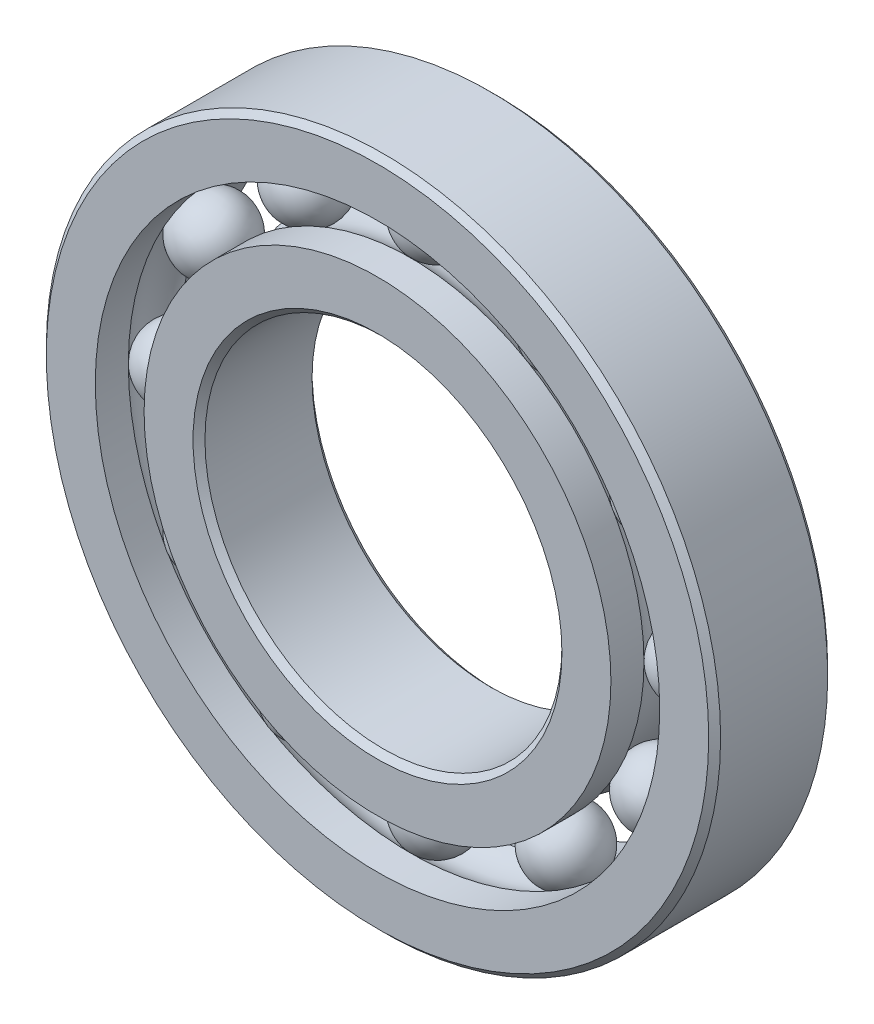
SolidWorks part; units mm, degrees
ref_plane "Front Plane" through (0, 0, 0) normal (0, 0, 1) x (1, 0, 0)
ref_plane "Top Plane" through (0, 0, 0) normal (0, 1, 0) x (1, 0, 0)
ref_plane "Right Plane" through (0, 0, 0) normal (1, 0, 0) x (0, 0, -1)
sketch "Sketch1" plane through (0, 0, 0) normal (1, 0, 0) x (0, 0, -1)
  line L0 (-4.7625, 0) -> (4.7625, 0) construction
  line L1 (0, 26.9875) -> (0, -26.9875) construction
  line L2 (4.2863, 26.9875) -> (-4.2863, 26.9875)
  line L3 (-4.2863, 26.9875) -> (-4.7625, 26.5112)
  line L4 (-4.7625, 26.5112) -> (-4.7625, 22.5913)
  line L5 (-4.7625, 22.5913) -> (-2.1167, 22.5913)
  line L6 (4.7625, 22.5913) -> (2.1167, 22.5913)
  line L7 (4.7625, 26.5112) -> (4.7625, 22.5913)
  line L8 (4.2863, 26.9875) -> (4.7625, 26.5112)
  line L9 (0, 26.9875) -> (0, 20.6375) construction
  line L10 (0, 20.6375) -> (0, 14.2875) construction
  arc A0 (-2.1167, 22.5913) -> (2.1167, 22.5913) centre (0, 20.6375) cw
  point P14 (0, 14.2875)
  dimension "Width" = 9.525
  dimension "OD" = 53.975
  dimension "D1" = 45
  dimension "D2" = 0.4763
  dimension "Shaft Dia" = 28.575
  dimension "D3" = 4.2333
  dimension "D4" = 1.9538
revolve "Revolve1" add sketch "Sketch1" angle 360 about L0
sketch "Sketch3" plane through (0, 0, 0) normal (1, 0, 0) x (0, 0, -1)
  line L0 (-4.7625, 18.6837) -> (-2.1167, 18.6837)
  line L1 (0, 26.9875) -> (0, -26.9875) construction
  line L2 (-4.7625, 26.5112) -> (-4.7625, 22.5913) construction
  line L3 (-4.7625, 18.6837) -> (-4.7625, 14.7638)
  line L4 (-4.2863, 26.9875) -> (-4.7625, 26.5112) construction
  line L5 (-4.7625, 14.7638) -> (-4.2863, 14.2875)
  line L6 (-4.2863, 14.2875) -> (4.2863, 14.2875)
  line L7 (4.2863, 26.9875) -> (4.2863, -26.9875) construction
  line L8 (4.2863, 14.2875) -> (4.7625, 14.7637)
  line L9 (4.7625, -26.5112) -> (4.7625, 26.5112) construction
  line L10 (4.7625, 14.7637) -> (4.7625, 18.6837)
  line L11 (4.7625, 18.6837) -> (2.1167, 18.6837)
  line L13 (4.2863, 26.9875) -> (4.7625, 26.5112) construction
  arc A0 (2.1167, 22.5913) -> (-2.1167, 22.5913) centre (0, 20.6375) ccw construction
  arc A1 (2.1167, 18.6837) -> (-2.1167, 18.6837) centre (0, 20.6375) cw
revolve "Revolve3" add sketch "Sketch3" angle 360 about L0
sketch "Sketch4" plane through (0, 0, 0) normal (1, 0, 0) x (0, 0, -1)
  line L0 (-2.8806, 20.6375) -> (2.8806, 20.6375)
  arc A2 (-2.8806, 20.6375) -> (2.8806, 20.6375) centre (0, 20.6375) cw
  arc A3 (2.1167, 22.5913) -> (-2.1167, 22.5913) centre (0, 20.6375) ccw construction
revolve "Revolve4" add sketch "Sketch4" angle 360 about L0
ref_axis "Axis1" through (0, 0, -4.7625) along (0, 0, 1)
pattern_circular "CirPattern1" count 12 every 30 about axis through (0, 0, -4.7625) along (0, 0, 1) of bodies 104
sketch "Sketch5" plane through (0, 0, 0) normal (1, 0, 0) x (0, 0, -1)
  line L0 (-4.7625, 22.5913) -> (-2.1167, 22.5913) construction
  line L1 (-4.5244, 22.5913) -> (-2.8806, 22.5913)
  line L2 (-4.5244, 22.5913) -> (-4.5244, 18.6837)
  line L3 (-4.5244, 18.6837) -> (-2.8806, 18.6837)
  line L4 (-2.8806, 22.5913) -> (-2.8806, 18.6837)
  line L5 (-4.7625, 18.6837) -> (-2.1167, 18.6837) construction
  line L6 (4.7625, 22.5913) -> (2.1167, 22.5913) construction
  line L7 (4.5244, 22.5913) -> (2.8806, 22.5913)
  line L8 (4.5244, 22.5913) -> (4.5244, 18.6837)
  line L9 (4.5244, 18.6837) -> (2.8806, 18.6837)
  line L10 (2.8806, 22.5913) -> (2.8806, 18.6837)
  line L11 (4.7625, 18.6837) -> (2.1167, 18.6837) construction
  line L12 (-4.2863, 26.9875) -> (-4.7625, 26.5112) construction
  point P18 (-4.5244, 26.7494)
revolve "Revolve5" [suppressed] add sketch "Sketch5" angle 360 about L0
equation "\"D2@Sketch1\" = \"Width@Sketch1\"*.05"
equation "\"D3@Sketch1\" = \"Width@Sketch1\"/2.25"
equation "\"D4@Sketch1\" = (((\"OD@Sketch1\"-\"Width@Sketch1\")/2)/3.25)/3.5"
equation "\"D2@CirPattern1\" = 360/\"Balls@CirPattern1\""
